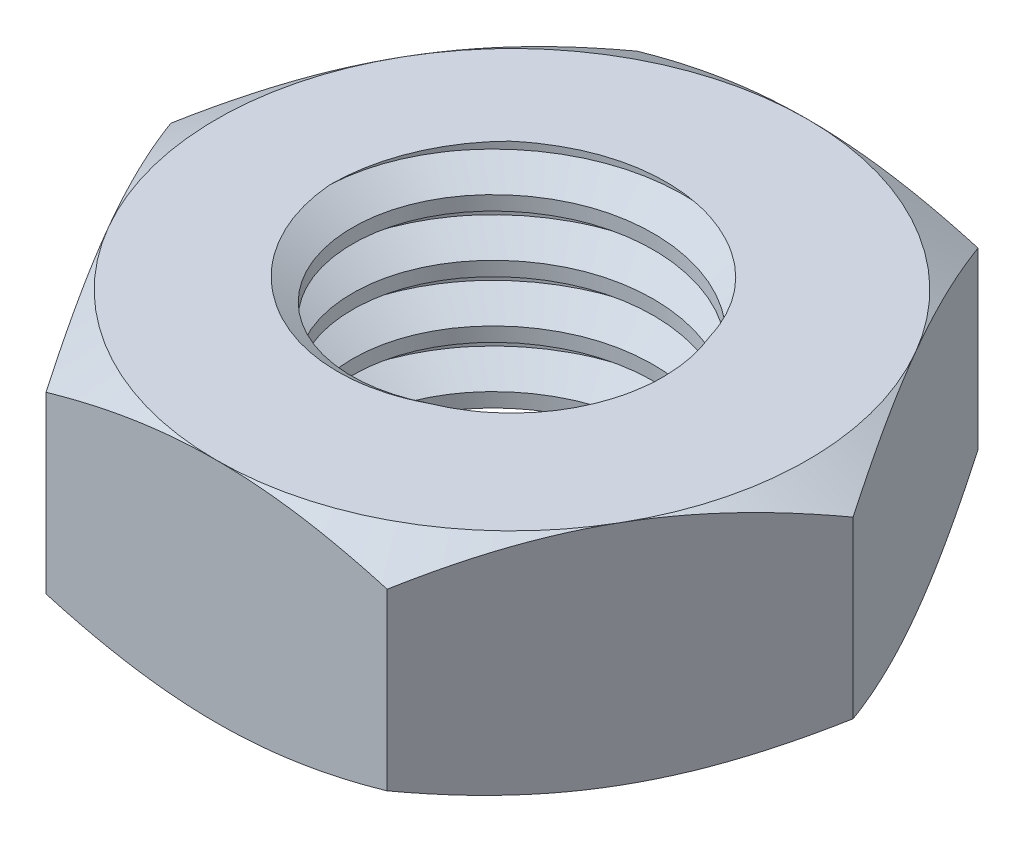
SolidWorks part; units mm, degrees
ref_plane "Front Plane" through (0, 0, 0) normal (0, 0, 1) x (1, 0, 0)
ref_plane "Top Plane" through (0, 0, 0) normal (0, 1, 0) x (1, 0, 0)
ref_plane "Right Plane" through (0, 0, 0) normal (1, 0, 0) x (0, 0, -1)
sketch "Sketch1" plane through (0, 0, 0) normal (0, 1, 0) x (1, 0, 0)
  line L1 (3, 0) -> (1.5, 2.5981)
  line L2 (1.5, 2.5981) -> (-1.5, 2.5981)
  line L3 (-1.5, 2.5981) -> (-3, 0)
  line L4 (-3, 0) -> (-1.5, -2.5981)
  line L5 (-1.5, -2.5981) -> (1.5, -2.5981)
  line L6 (1.5, -2.5981) -> (3, 0)
  circle A0 centre (0, 0) radius 2.5981 construction
  circle A1 centre (0, 0) radius 1.6
  dimension "D2" = 3.2
  dimension "D1" = 3
extrude "Boss-Extrude1" add sketch "Sketch1" along normal blind 2
thread "Thread1" pitch 0.5 method extrude profile "Thread Profile1" start angle 0, offset 1, length 4, pitch 0.5, diameter 3.2
ref_plane "Plane1" through (-1.6, 3, 0) normal (0, 0, 1) x (-1, 0, 0)
sketch "Thread Profile1" plane through (-1.6, 3, 0) normal (0, 0, 1) x (-1, 0, 0)
  line L0 (0, 0) -> (0, 0.5) construction
  line L11 (0, 0) -> (0, 0.4375)
  line L12 (0, 0.4375) -> (-0.2706, 0.2812)
  line L13 (-0.2706, 0.2812) -> (-0.2706, 0.1562)
  line L15 (-0.2706, 0.1562) -> (0, 0)
  line L17 (-0.2706, 0.2187) -> (0, 0.2187) construction
  point P2 (0, 0)
  dimension "Pitch" = 0.5
  dimension "Profile_Angle" = 60
  dimension "Profile_Land" = 0.125
  dimension "Profile_Height" = 0.2706
sketch "Sketch4" plane through (0, 0, -2.5981) normal (0, 0, -1) x (-1, 0, 0)
  line L0 (-3, 2) -> (-1.5, 2) construction
  line L1 (-1.7303, 2) -> (1.7432, 2)
  line L2 (-1.7303, 2) -> (-1.7303, 3.1396)
  line L3 (-1.7303, 3.1396) -> (1.7432, 3.1396)
  line L4 (1.7432, 2) -> (1.7432, 3.1396)
  line L5 (-3, 0) -> (-1.5, 0) construction
  line L6 (-1.7303, 0) -> (1.8393, 0)
  line L7 (-1.7303, 0) -> (-1.7303, -1.5195)
  line L8 (-1.7303, -1.5195) -> (1.8393, -1.5195)
  line L9 (1.8393, 0) -> (1.8393, -1.5195)
extrude "Cut-Extrude1" cut sketch "Sketch4" against normal blind 5
sketch "Sketch5" plane through (0, 2, 0) normal (0, 1, 0) x (1, 0, 0)
  circle A0 centre (0, 0) radius 2.5981
extrude "Cut-Extrude5" cut sketch "Sketch5" against normal through all draft 60 flip side to cut
sketch "Sketch6" plane through (0, 0, 0) normal (0, -1, 0) x (1, 0, 0)
  circle A0 centre (0, 0) radius 2.5981
extrude "Cut-Extrude6" cut sketch "Sketch6" against normal through all draft 60 flip side to cut
ref_axis "Axis1" through (0, 2.2868, 0) along (0, -1, 0)
